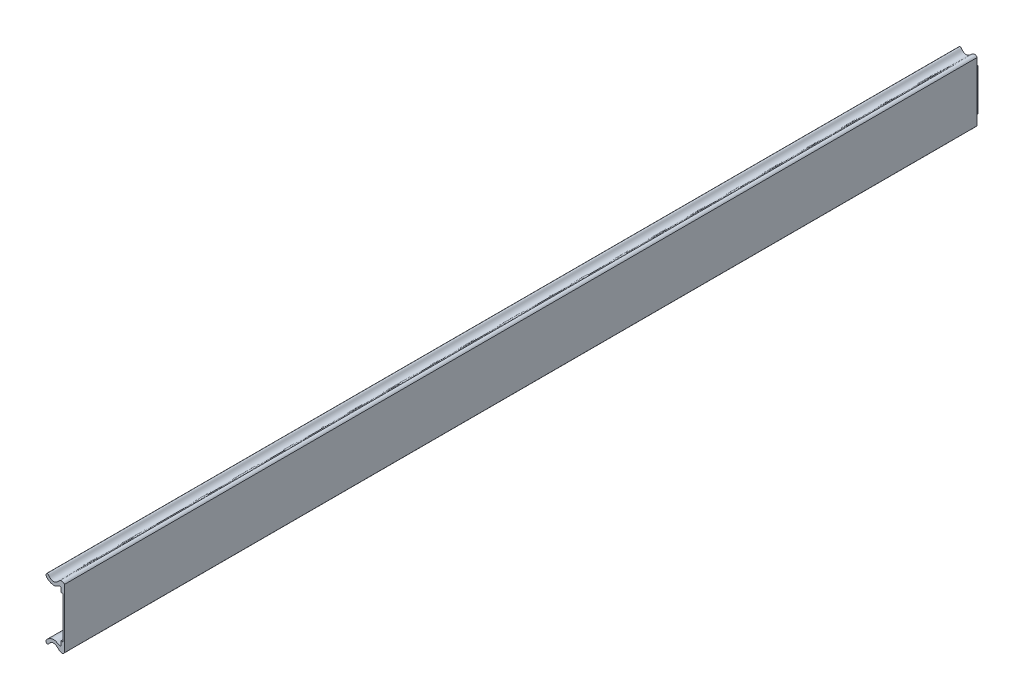
SolidWorks part; units mm, degrees
material "6061 Alloy"
ref_plane "Front Plane" through (0, 0, 0) normal (0, 0, 1) x (1, 0, 0)
ref_plane "Top Plane" through (0, 0, 0) normal (0, 1, 0) x (1, 0, 0)
ref_plane "Right Plane" through (0, 0, 0) normal (1, 0, 0) x (0, 0, -1)
sketch "Sketch4" plane through (0, 0, 0) normal (0, 0, 1) x (1, 0, 0)
  line L0 (11.6083, 3944.5639) -> (12.3116, 3944.5639)
  line L1 (12.3116, 3944.5639) -> (12.8641, 3944.5639)
  line L2 (12.3955, 3944.3764) -> (12.3955, 3928.523)
  line L3 (4.8646, 3944.3764) -> (4.8646, 3928.523)
  line L4 (12.3955, 3928.523) -> (4.8646, 3928.523)
  line L5 (12.3955, 3944.3764) -> (4.8646, 3944.3764)
  line L6 (12.8641, 3944.3764) -> (12.8641, 3928.523)
  line L7 (11.6083, 3928.3355) -> (12.8641, 3928.3355)
  line L8 (12.8641, 3925.2242) -> (12.8641, 3928.3355)
  line L9 (11.6037, 3945.881) -> (11.6037, 3944.3764)
  line L10 (11.6037, 3928.523) -> (11.6037, 3927.0184)
  line L11 (12.8641, 3944.5639) -> (12.8641, 3947.6752)
  spline S0 degree 2 poles (12.8641, 3928.523) (12.854, 3928.523) (12.8312, 3928.523) knots 0 0 0 0.25 0.25 0.25
  spline S1 degree 3 poles (12.8312, 3928.523) (12.8083, 3928.523) (12.7726, 3928.523) (12.7268, 3928.523) knots 0.25 0.25 0.25 0.25 0.5 0.5 0.5 0.5
  spline S2 degree 3 poles (12.7268, 3928.523) (12.6811, 3928.523) (12.6257, 3928.523) (12.568, 3928.523) knots 0.5 0.5 0.5 0.5 0.75 0.75 0.75 0.75
  spline S3 degree 3 poles (12.568, 3928.523) (12.5103, 3928.523) (12.4507, 3928.523) (12.3955, 3928.523) knots 0.75 0.75 0.75 0.75 1 1 1 1
  spline S4 degree 2 poles (12.8641, 3944.3764) (12.854, 3944.3764) (12.8312, 3944.3764) knots 0 0 0 0.25 0.25 0.25
  spline S5 degree 3 poles (12.8312, 3944.3764) (12.8083, 3944.3764) (12.7726, 3944.3764) (12.7268, 3944.3764) knots 0.25 0.25 0.25 0.25 0.5 0.5 0.5 0.5
  spline S6 degree 3 poles (12.7268, 3944.3764) (12.6811, 3944.3764) (12.6257, 3944.3764) (12.568, 3944.3764) knots 0.5 0.5 0.5 0.5 0.75 0.75 0.75 0.75
  spline S7 degree 3 poles (12.568, 3944.3764) (12.5103, 3944.3764) (12.4507, 3944.3764) (12.3955, 3944.3764) knots 0.75 0.75 0.75 0.75 1 1 1 1
  spline S8 degree 2 poles (11.6083, 3944.3764) (11.6083, 3944.3947) (11.6083, 3944.4313) knots 0 0 0 0.5 0.5 0.5
  spline S9 degree 3 poles (11.6083, 3944.4313) (11.6083, 3944.4679) (11.6083, 3944.5197) (11.6083, 3944.5639) knots 0.5 0.5 0.5 0.5 1 1 1 1
  spline S10 degree 3 poles (12.8641, 3944.5639) (12.8641, 3944.5197) (12.8641, 3944.4679) (12.8641, 3944.4313) knots 0 0 0 0 0.5 0.5 0.5 0.5
  spline S11 degree 2 poles (12.8641, 3944.4313) (12.8641, 3944.3947) (12.8641, 3944.3764) knots 0.5 0.5 0.5 1 1 1
  spline S12 degree 3 poles (11.6083, 3928.3355) (11.6083, 3928.3797) (11.6083, 3928.4315) (11.6083, 3928.4681) knots 0 0 0 0 0.5 0.5 0.5 0.5
  spline S13 degree 2 poles (11.6083, 3928.4681) (11.6083, 3928.5047) (11.6083, 3928.523) knots 0.5 0.5 0.5 1 1 1
  spline S14 degree 2 poles (12.8641, 3928.523) (12.8641, 3928.5047) (12.8641, 3928.4681) knots 0 0 0 0.5 0.5 0.5
  spline S15 degree 3 poles (12.8641, 3928.4681) (12.8641, 3928.4315) (12.8641, 3928.3797) (12.8641, 3928.3355) knots 0.5 0.5 0.5 0.5 1 1 1 1
  spline S16 degree 3 poles (11.6037, 3927.0184) (11.6115, 3926.8536) (11.5099, 3926.7103) (11.1995, 3926.6172) (10.9962, 3926.6814) (10.628, 3926.8676) (10.4944, 3926.9447) (10.2069, 3927.1095) (10.053, 3927.1961) (9.7272, 3927.3498) (9.5553, 3927.4166) (9.0158, 3927.5472) (8.6241, 3927.5464) (7.9951, 3927.3964) (7.7772, 3927.3205) (7.3501, 3927.1338) (7.1411, 3927.0231) (6.759, 3926.7851) (6.5872, 3926.6587) (6.1517, 3926.2721) (5.9653, 3926.0004) (5.8484, 3925.4722) (5.9719, 3924.9728) (6.3938, 3924.863) (6.685, 3924.9771) (6.7746, 3925.051) (6.9521, 3925.2451) (7.0414, 3925.3641) (7.2433, 3925.6123) (7.3572, 3925.7413) (7.6233, 3925.9774) (7.7736, 3926.085) (8.1057, 3926.2511) (8.2877, 3926.3093) (8.8742, 3926.3707) (9.3128, 3926.2701) (9.8434, 3926.0009) (9.9962, 3925.891) (10.2709, 3925.6558) (10.3933, 3925.5307) (10.6281, 3925.2912) (10.7408, 3925.1784) (11.0339, 3924.9295) (11.22, 3924.8078) (11.5219, 3924.6929) (11.6021, 3924.6673) (12.0268, 3924.5751) (12.438, 3924.6267) (12.8641, 3925.2242) knots 0 0 0 0 0.0625 0.0625 0.125 0.125 0.15625 0.15625 0.1875 0.1875 0.21875 0.21875 0.28125 0.28125 0.3125 0.3125 0.34375 0.34375 0.375 0.375 0.4375 0.4375 0.5 0.5625 0.5625 0.59375 0.59375 0.625 0.625 0.65625 0.65625 0.6875 0.6875 0.71875 0.71875 0.78125 0.78125 0.8125 0.8125 0.84375 0.84375 0.875 0.875 0.921875 0.921875 0.9375 0.9375 1 1 1 1
  spline S17 degree 3 poles (12.8641, 3947.6752) (12.438, 3948.2727) (12.0268, 3948.3243) (11.6021, 3948.2321) (11.5219, 3948.2065) (11.22, 3948.0916) (11.0339, 3947.9699) (10.7408, 3947.721) (10.6281, 3947.6082) (10.3933, 3947.3687) (10.2709, 3947.2436) (9.9962, 3947.0084) (9.8434, 3946.8985) (9.3128, 3946.6293) (8.8742, 3946.5287) (8.2877, 3946.5901) (8.1057, 3946.6483) (7.7736, 3946.8144) (7.6233, 3946.922) (7.3572, 3947.1581) (7.2433, 3947.2871) (7.0414, 3947.5353) (6.9521, 3947.6543) (6.7746, 3947.8484) (6.685, 3947.9223) (6.3938, 3948.0364) (5.9719, 3947.9266) (5.8484, 3947.4272) (5.9653, 3946.899) (6.1517, 3946.6273) (6.5872, 3946.2407) (6.759, 3946.1143) (7.1411, 3945.8763) (7.3501, 3945.7656) (7.7772, 3945.5789) (7.9951, 3945.503) (8.6241, 3945.353) (9.0158, 3945.3522) (9.5553, 3945.4828) (9.7272, 3945.5496) (10.053, 3945.7033) (10.2069, 3945.7899) (10.4944, 3945.9547) (10.628, 3946.0318) (10.9962, 3946.218) (11.1995, 3946.2822) (11.5099, 3946.1891) (11.6115, 3946.0458) (11.6037, 3945.881) knots 0 0 0 0 0.0625 0.0625 0.078125 0.078125 0.125 0.125 0.15625 0.15625 0.1875 0.1875 0.21875 0.21875 0.28125 0.28125 0.3125 0.3125 0.34375 0.34375 0.375 0.375 0.40625 0.40625 0.4375 0.4375 0.5 0.5625 0.5625 0.625 0.625 0.65625 0.65625 0.6875 0.6875 0.71875 0.71875 0.78125 0.78125 0.8125 0.8125 0.84375 0.84375 0.875 0.875 0.9375 0.9375 1 1 1 1
extrude "Boss-Extrude1" add sketch "Sketch4" along normal blind 346.02 contours L11 S17 L9 L5 S8 S9 L0 L1 | S6 S7 L2 S3 S2 S1 S0 L6 S4 S5 | L10 S16 L8 L7 S12 S13 L4 | S11 S10 L1 L0 S9 S8 L5 S7 S6 S5 S4 | S15 S14 S0 S1 S2 S3 L4 S13 S12 L7 region at (10.0699, 3946.5182, 0) region at (12.2362, 3944.4702, 0) region at (12.6298, 3936.4497, 0) region at (12.2362, 3928.4292, 0) region at (10.0699, 3926.3812, 0)
sketch "Sketch5" plane through (0, 0, 0) normal (0, 0, -1) x (-1, 0, 0)
  line L0 (-12.3955, 3936.4497) -> (-12.8641, 3936.4497) construction
  line L1 (-12.3955, 3944.3764) -> (-12.3955, 3928.523) construction
  line L2 (-12.8641, 3947.6752) -> (-12.8641, 3925.2242) construction
ref_plane "MidPlane" through (0, 3936.4497, 0) normal (0, 1, 0) x (1, 0, 0)
extrude "Boss-Extrude2" add sketch "Sketch4<3>" against normal blind 0.8 contours L2 L5 L3 L4 region at (8.6301, 3936.4497, 0)
sketch "Sketch4<3>" plane through (0, 0, 0) normal (0, 0, 1) x (1, 0, 0) same geometry as "Sketch4"
